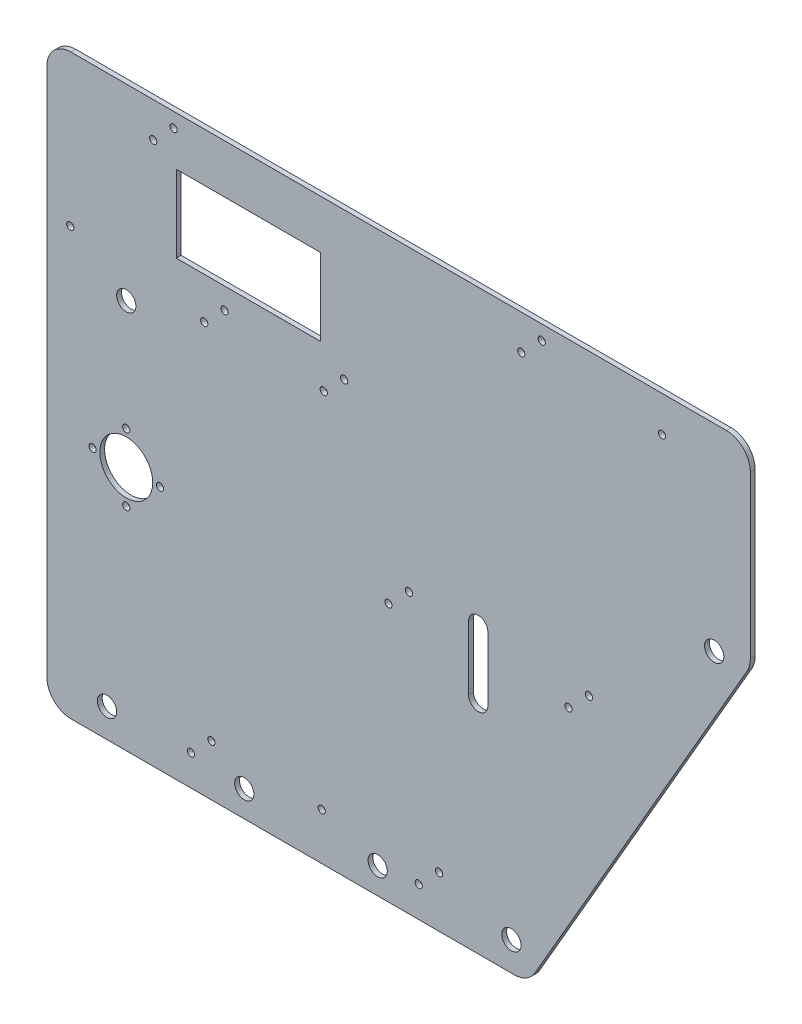
SolidWorks part; units mm, degrees
ref_plane "Front Plane" through (0, 0, 0) normal (0, 0, 1) x (1, 0, 0)
ref_plane "Top Plane" through (0, 0, 0) normal (0, 1, 0) x (1, 0, 0)
ref_plane "Right Plane" through (0, 0, 0) normal (1, 0, 0) x (0, 0, -1)
sketch "Sketch1" plane through (0, 0, 0) normal (0, 0, 1) x (1, 0, 0)
  line L0 (100, 80) -> (192.376, 80)
  line L1 (-100, -80) -> (100, -80)
  line L2 (-100, -80) -> (-100, 80)
  line L3 (-100, 80) -> (100, 80)
  line L4 (100, -80) -> (100, 80)
  line L5 (-100, -80) -> (100, 80) construction
  line L6 (-100, 80) -> (100, -80) construction
  line L7 (192.376, 80) -> (100, -80)
  line L8 (100, 80) -> (100, -80)
  line L10 (-100, 80) -> (192.376, 80)
  line L11 (-100, 80) -> (-100, 110)
  line L12 (-100, 110) -> (192.376, 110)
  line L13 (192.376, 80) -> (192.376, 110)
  point P0 (0, 0)
  dimension "D1" = 160
  dimension "D2" = 200
  dimension "D3" = 30
  dimension "D4" = 30
extrude "Boss-Extrude1" add sketch "Sketch1" along normal blind 2 contours L1 L4 L3 L2 | L7 L0 L4 | L11 L10 L13 L12 region at (0, 0, 0) region at (130.792, 26.6667, 0)
sketch "Sketch2" plane through (0, 0, 2) normal (0, 0, 1) x (1, 0, 0)
  line L0 (-100, -80) -> (100, -80) construction
  line L1 (192.376, 80) -> (100, -80) construction
  line L2 (79.2904, 11.2418) -> (79.2904, 37.9086) construction
  line L3 (-100, -80) -> (-100, 110) construction
  line L4 (-100, 110) -> (192.376, 110) construction
  line L7 (-100, 110) -> (192.376, 110) construction
  line L8 (75.2904, 11.2418) -> (75.2904, 37.9086)
  line L11 (-100, -80) -> (-100, 110) construction
  line L12 (83.2904, 11.2418) -> (83.2904, 37.9086)
  line L13 (-100, -80) -> (-100, 110) construction
  line L14 (-67, 22) -> (-67, 85.6687) construction
  circle A0 centre (93.0718, -68) radius 4
  circle A1 centre (177.3649, 78) radius 4
  circle A2 centre (-67, 22) radius 11
  circle A3 centre (-75, -68) radius 4
  circle A4 centre (-53, 22) radius 1.5
  circle A5 centre (-67, 36) radius 1.5
  circle A6 centre (-81, 22) radius 1.5
  circle A7 centre (-67, 8) radius 1.5
  circle A11 centre (54.5495, -67.2426) radius 1.5
  circle A12 centre (63.0348, -58.7574) radius 1.5
  circle A13 centre (14.2259, -60.5) radius 1.5
  circle A14 centre (-40.1271, -67.2426) radius 1.5
  circle A15 centre (-31.6419, -58.7574) radius 1.5
  circle A16 centre (-90.2956, 97.2169) radius 1.5
  circle A17 centre (-34.6051, 90.4743) radius 1.5
  circle A18 centre (-26.1198, 98.9596) radius 1.5
  circle A19 centre (15.0782, 90.4743) radius 1.5
  circle A20 centre (23.5635, 98.9596) radius 1.5
  circle A21 centre (41.9695, 27.4743) radius 1.5
  circle A22 centre (50.4548, 35.9596) radius 1.5
  circle A23 centre (-39.813, 27.4743) radius 1.5 construction
  circle A24 centre (-31.3277, 35.9596) radius 1.5 construction
  circle A25 centre (116.8113, 27.4743) radius 1.5
  circle A26 centre (125.2966, 35.9596) radius 1.5
  circle A27 centre (79.2904, 25) radius 4 construction
  circle A31 centre (155.6518, 145.1456) radius 1.5
  arc A32 (75.2904, 11.2418) -> (83.2904, 11.2418) centre (79.2904, 11.2418) ccw
  arc A33 (83.2904, 37.9086) -> (75.2904, 37.9086) centre (79.2904, 37.9086) ccw
  circle A34 centre (-55.8147, 145.4743) radius 1.5
  circle A35 centre (-47.3294, 153.9596) radius 1.5
  circle A36 centre (97.1924, 145.4743) radius 1.5
  circle A37 centre (105.6777, 153.9596) radius 1.5
  circle A38 centre (-17.9479, -69.1174) radius 4
  circle A39 centre (37.4944, -69.1174) radius 4
  circle A40 centre (-67, 22) radius 40 construction
  circle A41 centre (-67, 82) radius 20 construction
  circle A42 centre (-67, 82) radius 4
  point P87 (79.2904, 24.5752)
  dimension "D3" = 8
  dimension "D4" = 8
  dimension "D9" = 22
  dimension "D10" = 8
  dimension "D12" = 3
  dimension "D13" = 3
  dimension "D14" = 3
  dimension "D15" = 3
  dimension "D16" = 14
  dimension "D20" = 13.3334
  dimension "D22" = 179.2904
  dimension "D25" = 3
  dimension "D26" = 3
  dimension "D29" = 8
  dimension "D28" = 3
  dimension "D31" = 8
  dimension "D32" = 8
  dimension "D23" = 12.9086
  dimension "D24" = 80
  dimension "D34" = 40
  dimension "D35" = 8
  dimension "D1" = 12
  dimension "D2" = 12
  dimension "D5" = 32
  dimension "D6" = 12
  dimension "D7" = 88
  dimension "D8" = 33
  dimension "D11" = 12
  dimension "D17" = 14
  dimension "D18" = 14
  dimension "D19" = 14
  dimension "D21" = 85.4248
  dimension "D27" = 25
  dimension "D30" = 8
  dimension "D33" = 60
extrude "Cut-Extrude1" cut sketch "Sketch2" against normal blind 3
sketch "Sketch4" plane through (0, 0, 2) normal (0, 0, 1) x (1, 0, 0)
  line L0 (192.376, 80) -> (192.376, 110) construction
  line L1 (-100, 110) -> (192.376, 110)
  line L2 (-100, 110) -> (-100, 160)
  line L3 (-100, 160) -> (192.376, 160)
  line L4 (192.376, 110) -> (192.376, 160)
  dimension "D1" = 50
extrude "Boss-Extrude2" add sketch "Sketch4" against normal blind 2
fillet "Fillet1" radius 10 5 edges at (192.376, 160, 1) (192.376, 80, 1) (100, -80, 1) (-100, -80, 1) (-100, 160, 1)
sketch "Sketch5" plane through (0, 0, 2) normal (0, 0, 1) x (1, 0, 0)
  line L1 (-46.1781, 107.7169) -> (13.8219, 107.7169)
  line L2 (-46.1781, 107.7169) -> (-46.1781, 139.7169)
  line L3 (-46.1781, 139.7169) -> (13.8219, 139.7169)
  line L4 (13.8219, 107.7169) -> (13.8219, 139.7169)
  circle A2 centre (-55.8147, 145.4743) radius 1.5
  circle A3 centre (-47.3294, 153.9596) radius 1.5
  circle A4 centre (97.1924, 145.4743) radius 1.5
  circle A5 centre (105.6777, 153.9596) radius 1.5
  circle A6 centre (155.6518, 145.1456) radius 1.5
  dimension "D1" = 3
extrude "Cut-Extrude2" cut sketch "Sketch5" against normal blind 11
